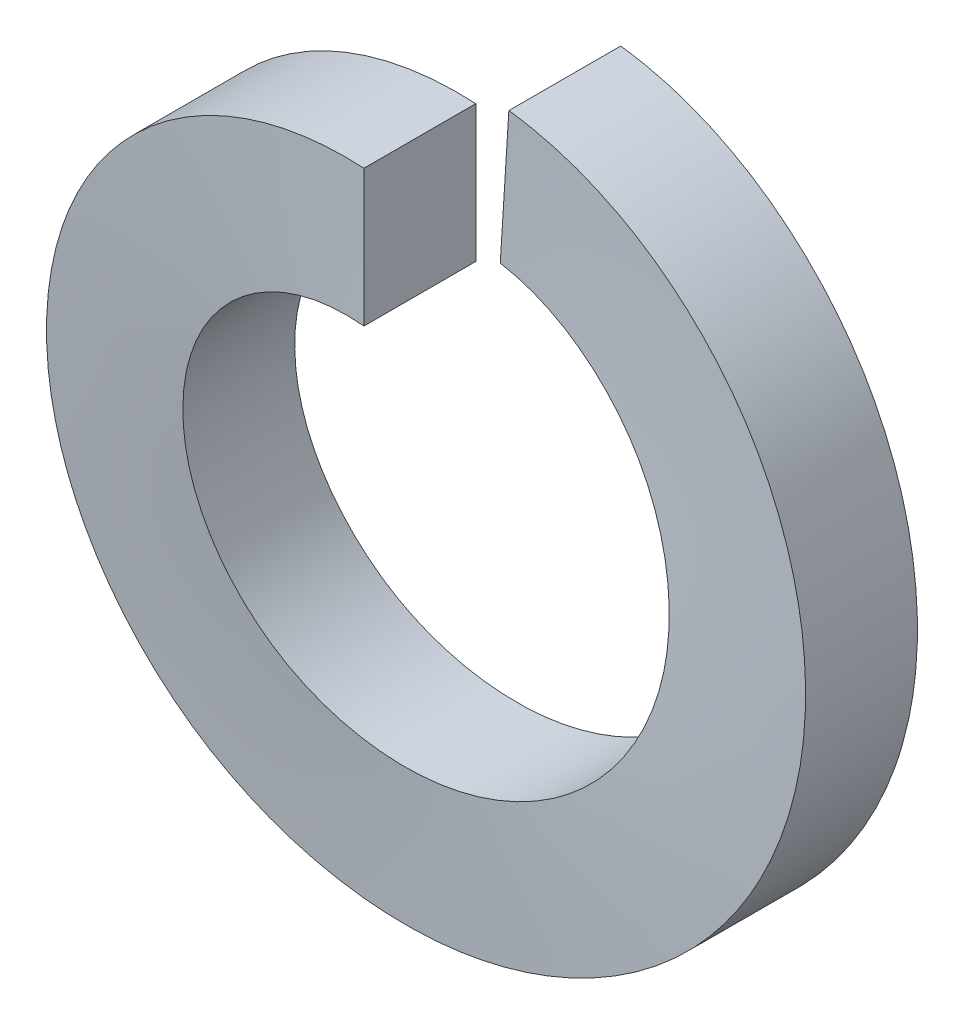
SolidWorks part; units mm, degrees
material "Chrome Stainless Steel"
ref_plane "Front Plane" through (0, 0, 0) normal (0, 0, 1) x (1, 0, 0)
ref_plane "Top Plane" through (0, 0, 0) normal (0, 1, 0) x (1, 0, 0)
ref_plane "Right Plane" through (0, 0, 0) normal (1, 0, 0) x (0, 0, -1)
ref_axis "CentralAxis" through (0, 0, -1.0922) along (0, 0, 1)
sketch "Sketch1" plane through (0, 0, 0) normal (0, 0, 1) x (1, 0, 0)
  line L0 (0, 2.8) -> (0, 1.7) construction
  circle A0 centre (0, 0) radius 2.8
  circle A1 centre (0, 0) radius 1.7 construction
  dimension "ID" = 3.4
  dimension "OD" = 5.6
curve "Helix/Spiral1" pitch 1 height 0.99 radius 2.8 left hand yes centre (0, 0, 0) axis (0, 0, -1) start towards (0, 1, 0) parameters "HT"=0.99
sketch "Sketch2" plane through (0, 0, 0) normal (1, 0, 0) x (0, 0, -1)
  line L1 (0, 2.8) -> (-0.9, 2.8)
  line L2 (0, 2.8) -> (0, 1.7)
  line L3 (0, 1.7) -> (-0.9, 1.7)
  line L4 (-0.9, 2.8) -> (-0.9, 1.7)
  dimension "THK" = 0.9
sweep "Sweep1" add profiles "Sketch2" path "Helix/Spiral1"
equation "\"HT@Helix/Spiral1\" = \"THK@Sketch2\"*1.1"
